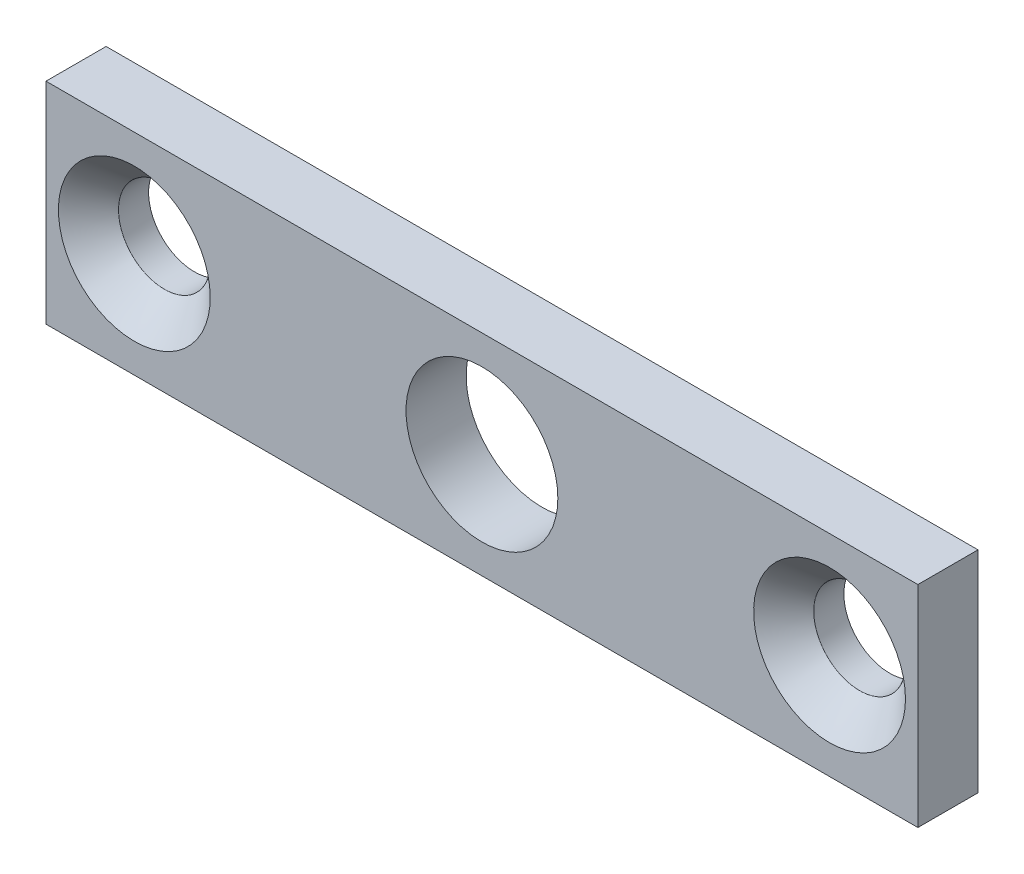
SolidWorks part; units mm, degrees
ref_plane "前视基准面" through (0, 0, 0) normal (0, 0, 1) x (1, 0, 0)
ref_plane "上视基准面" through (0, 0, 0) normal (0, 1, 0) x (1, 0, 0)
ref_plane "右视基准面" through (0, 0, 0) normal (1, 0, 0) x (0, 0, -1)
sketch "草图1" plane through (0, 0, 0) normal (0, 0, 1) x (1, 0, 0)
  line L0 (0, 0) -> (46.25, 0) construction
  line L2 (-5.875, -7) -> (52.125, -7)
  line L3 (-5.875, -7) -> (-5.875, 7)
  line L4 (-5.875, 7) -> (52.125, 7)
  line L5 (52.125, -7) -> (52.125, 7)
  line L6 (-5.875, -7) -> (52.125, 7) construction
  line L7 (-5.875, 7) -> (52.125, -7) construction
  circle A0 centre (0, 0) radius 3.05
  circle A1 centre (46.25, 0) radius 3.05
  circle A2 centre (23.125, 0) radius 5.05
  dimension "D1" = 58
  dimension "D4" = 10.1
  dimension "D5" = 6.1
  dimension "D6" = 6.1
  dimension "D2" = 14
  dimension "D3" = 46.25
extrude "凸台-拉伸1" add sketch "草图1" along normal blind 4
fillet "圆角1" radius 2 2 edges at (49.3, 0, 4) (3.05, 0, 4) conic radius 100
